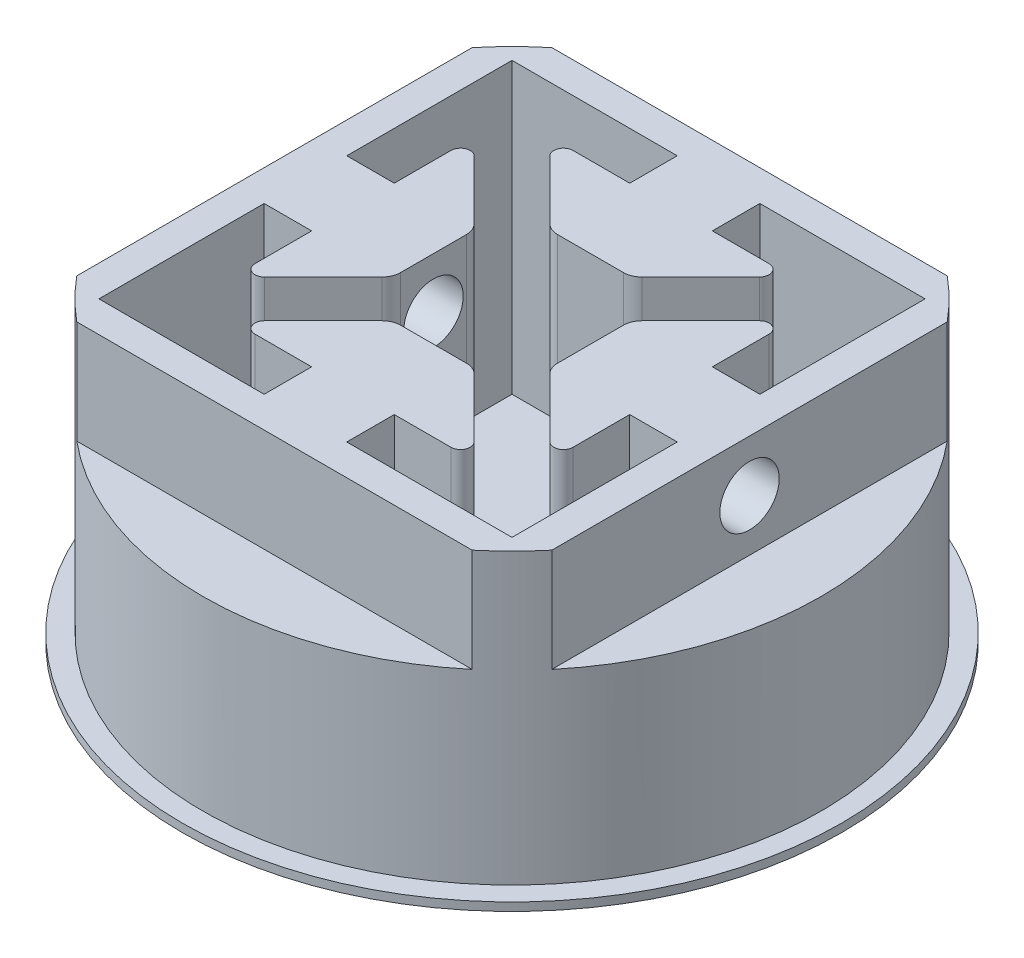
SolidWorks part; units mm, degrees
ref_plane "Front" through (0, 0, 0) normal (0, 0, 1) x (1, 0, 0)
ref_plane "Top" through (0, 0, 0) normal (0, 1, 0) x (1, 0, 0)
ref_plane "Right" through (0, 0, 0) normal (1, 0, 0) x (0, 0, -1)
sketch "Skizze1" plane through (0, 0, 0) normal (0, 1, 0) x (1, 0, 0)
  line L0 (0, 20) -> (0, -0.3392) construction
  line L1 (-20, -20) -> (-4, -20)
  line L2 (-20, -20) -> (-20, -4)
  line L3 (-20, 20) -> (-4, 20)
  line L4 (20, -20) -> (20, -4)
  line L5 (-20, -20) -> (20, 20) construction
  line L6 (-20, 20) -> (20, -20) construction
  line L7 (4, 20) -> (4, 15.4)
  line L8 (4, 15.4) -> (11.7329, 15.4)
  line L9 (11.7329, 15.4) -> (3.9329, 7.6)
  line L10 (3.9329, 7.6) -> (-3.9329, 7.6)
  line L11 (-11.7329, 15.4) -> (-3.9329, 7.6)
  line L12 (-4, 15.4) -> (-11.7329, 15.4)
  line L13 (-4, 20) -> (-4, 15.4)
  line L14 (4, 20) -> (20, 20)
  line L18 (20, 4) -> (15.4, 4)
  line L19 (15.4, 4) -> (15.4, 11.7329)
  line L20 (15.4, 11.7329) -> (7.6, 3.9329)
  line L21 (7.6, 3.9329) -> (7.6, -3.9329)
  line L22 (15.4, -11.7329) -> (7.6, -3.9329)
  line L23 (15.4, -4) -> (15.4, -11.7329)
  line L24 (20, -4) -> (15.4, -4)
  line L25 (20, 4) -> (20, 20)
  line L26 (-15.4, 4) -> (-15.4, 11.7329)
  line L27 (-15.4, 11.7329) -> (-7.6, 3.9329)
  line L28 (-7.6, -3.9329) -> (-7.6, 3.9329)
  line L29 (-15.4, -11.7329) -> (-7.6, -3.9329)
  line L30 (-15.4, -4) -> (-15.4, -11.7329)
  line L31 (-20, -4) -> (-15.4, -4)
  line L32 (-20, 4) -> (-15.4, 4)
  line L33 (4, -20) -> (4, -15.4)
  line L34 (4, -15.4) -> (11.7329, -15.4)
  line L35 (11.7329, -15.4) -> (3.9329, -7.6)
  line L36 (-3.9329, -7.6) -> (3.9329, -7.6)
  line L37 (-11.7329, -15.4) -> (-3.9329, -7.6)
  line L38 (-4, -15.4) -> (-11.7329, -15.4)
  line L39 (-4, -20) -> (-4, -15.4)
  line L40 (-20, 4) -> (-20, 20)
  line L41 (4, -20) -> (20, -20)
  circle A0 centre (0, 0) radius 29.925
  arc A1 (9.4888, 15.4) -> (10.1461, 13.8132) centre (9.4888, 14.4705) cw
  arc A3 (4.459, 8.126) -> (3.189, 7.6) centre (3.189, 9.396) cw
  arc A4 (-4.459, 8.126) -> (-3.189, 7.6) centre (-3.189, 9.396) ccw
  arc A5 (-9.4888, 15.4) -> (-10.1461, 13.8132) centre (-9.4888, 14.4705) ccw
  arc A6 (15.4, 9.4888) -> (13.8132, 10.1461) centre (14.4705, 9.4888) ccw
  arc A7 (8.126, 4.459) -> (7.6, 3.189) centre (9.396, 3.189) ccw
  arc A8 (8.126, -4.459) -> (7.6, -3.189) centre (9.396, -3.189) cw
  arc A9 (15.4, -9.4888) -> (13.8132, -10.1461) centre (14.4705, -9.4888) cw
  arc A10 (-15.4, 9.4888) -> (-13.8132, 10.1461) centre (-14.4705, 9.4888) cw
  arc A11 (-8.126, 4.459) -> (-7.6, 3.189) centre (-9.396, 3.189) cw
  arc A12 (-8.126, -4.459) -> (-7.6, -3.189) centre (-9.396, -3.189) ccw
  arc A13 (-15.4, -9.4888) -> (-13.8132, -10.1461) centre (-14.4705, -9.4888) ccw
  arc A14 (9.4888, -15.4) -> (10.1461, -13.8132) centre (9.4888, -14.4705) ccw
  arc A15 (4.459, -8.126) -> (3.189, -7.6) centre (3.189, -9.396) ccw
  arc A16 (-4.459, -8.126) -> (-3.189, -7.6) centre (-3.189, -9.396) cw
  arc A17 (-9.4888, -15.4) -> (-10.1461, -13.8132) centre (-9.4888, -14.4705) cw
  point P0 (0, 0)
  point P16 (0, 7.6)
  dimension "D2" = 59.85
  dimension "D1" = 40
  dimension "D3" = 8
  dimension "D5" = 4.6
extrude "Aufsatz-Linear austragen1" add sketch "Skizze1" along normal blind 28 contours A0 A17 L38 L39 L1 L2 L31 L30 A13 L29 A12 L28 A11 L27 A10 L26 L32 L40 L3 L13 L12 A5 L11 A4 L10 A3 L9 A1 L8 L7 L14 L25 L18 L19 A6 L20 A7 L21 A8 L22 A9 L23 L24 L4 L41 L33 L34 A14 L35 A15 region at (-29.0786, 0, 0)
ref_plane "Ebene1" through (23, 0, 0) normal (-1, 0, 0) x (0, 0, 1)
sketch "Skizze3" plane through (23, 0, 0) normal (-1, 0, 0) x (0, 0, 1)
  line L0 (0, 0) -> (0, 28) construction
  line L1 (-3.189, 28) -> (3.189, 28) construction
  line L2 (29.925, 28) -> (-29.925, 28) construction
  circle A0 centre (0, 23) radius 2.875
  dimension "D1" = 5.75
  dimension "D2" = 5
extrude "Schnitt-Linear austragen1" cut sketch "Skizze3" along normal up to next and the other way blind 10
sketch "Skizze4" plane through (23, 0, 0) normal (-1, 0, 0) x (0, 0, 1)
  line L0 (-29.925, 14) -> (29.925, 14) construction
  line L1 (-29.925, 28) -> (-29.925, 0) construction
  line L2 (29.925, 0) -> (29.925, 28) construction
  line L3 (-29.925, 18) -> (29.925, 18)
  line L4 (29.925, 18) -> (29.925, 28)
  line L5 (29.925, 28) -> (-29.925, 28)
  line L6 (-29.925, 28) -> (-29.925, 18)
  dimension "D1" = 10
extrude "Schnitt-Linear austragen2" cut sketch "Skizze4" against normal blind 10
pattern_circular "Kreismuster1" count 2 over 360 about axis through (0, 28, 0) along (0, -1, 0) of "Schnitt-Linear austragen1" reverse direction yes
pattern_circular "Kreismuster2" count 4 over 360 about axis through (0, 28, 0) along (0, -1, 0) of "Schnitt-Linear austragen2" reverse direction yes
sketch "Skizze5" plane through (0, 0, 0) normal (0, -1, 0) x (1, 0, 0)
  circle A0 centre (0, 0) radius 31.925
  circle A2 centre (0, 0) radius 29.925 construction
  dimension "D1" = 2
extrude "Aufsatz-Linear austragen2" add sketch "Skizze5" along normal blind 0.8
